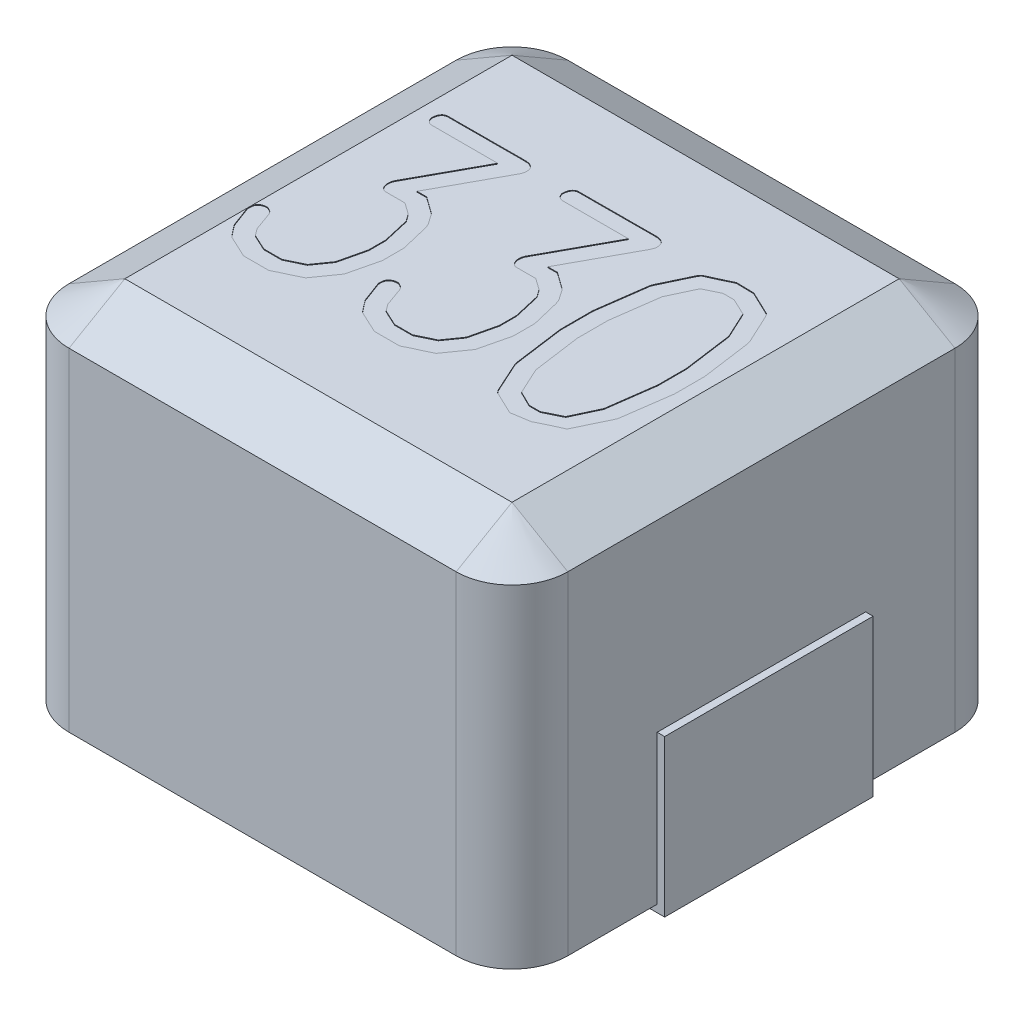
SolidWorks part; units mm, degrees
ref_plane "Front Plane" through (0, 0, 0) normal (0, 0, 1) x (1, 0, 0)
ref_plane "Top Plane" through (0, 0, 0) normal (0, 1, 0) x (1, 0, 0)
ref_plane "Right Plane" through (0, 0, 0) normal (1, 0, 0) x (0, 0, -1)
sketch "Sketch1" plane through (0, 0, 0) normal (0, 1, 0) x (1, 0, 0)
  line L0 (0, 6.4257) -> (0, -7.6623) construction
  line L1 (-1.025, 3.35) -> (1.025, 3.35) construction
  line L2 (-3.35, 1.525) -> (-3.35, -1.525) construction
  line L3 (-1.025, -3.35) -> (1.025, -3.35) construction
  line L4 (3.35, 1.525) -> (3.35, -1.525) construction
  line L5 (-1.675, 1.675) -> (1.675, -1.675) construction
  line L6 (-1.675, -1.675) -> (1.675, 1.675) construction
  line L7 (-1.175, 3.2) -> (-1.175, 1.825) construction
  line L8 (-1.325, 1.675) -> (-3.2, 1.675) construction
  line L9 (0, 0) -> (-4.3179, 0) construction
  line L10 (1.325, 1.675) -> (3.2, 1.675) construction
  line L11 (1.175, 3.2) -> (1.175, 1.825) construction
  line L12 (-1.325, -1.675) -> (-3.2, -1.675) construction
  line L13 (1.325, -1.675) -> (3.2, -1.675) construction
  line L14 (1.175, -3.2) -> (1.175, -1.825) construction
  line L15 (-1.175, -3.2) -> (-1.175, -1.825) construction
  line L16 (-3.35, 3.35) -> (-1.175, 3.35) construction
  line L17 (-3.35, 3.35) -> (-1.675, 1.675) construction
  line L18 (-3.35, 3.35) -> (-3.35, 1.675) construction
  line L19 (1.175, 3.35) -> (3.35, 3.35) construction
  line L20 (1.675, 1.675) -> (3.35, 3.35) construction
  line L21 (3.35, 3.35) -> (3.35, 1.675) construction
  line L22 (3.35, -1.675) -> (3.35, -3.35) construction
  line L23 (1.675, -1.675) -> (3.35, -3.35) construction
  line L24 (1.175, -3.35) -> (3.35, -3.35) construction
  line L25 (-3.35, -3.35) -> (-1.175, -3.35) construction
  line L26 (-3.35, -3.35) -> (-1.675, -1.675) construction
  line L27 (-3.35, -1.675) -> (-3.35, -3.35) construction
  line L29 (2.6, -3.35) -> (-2.6, -3.35)
  line L30 (3.35, -2.6) -> (3.35, 2.6)
  line L31 (2.6, 3.35) -> (-2.6, 3.35)
  line L32 (-3.35, -2.6) -> (-3.35, 2.6)
  line L33 (3.35, -3.35) -> (-3.35, 3.35) construction
  line L34 (3.35, 3.35) -> (-3.35, -3.35) construction
  arc A0 (3.35, -1.525) -> (3.2, -1.675) centre (3.2, -1.525) cw construction
  arc A1 (1.325, -1.675) -> (1.175, -1.825) centre (1.325, -1.825) ccw construction
  arc A2 (1.175, -3.2) -> (1.025, -3.35) centre (1.025, -3.2) cw construction
  arc A3 (-1.025, -3.35) -> (-1.175, -3.2) centre (-1.025, -3.2) cw construction
  arc A4 (-1.175, -1.825) -> (-1.325, -1.675) centre (-1.325, -1.825) ccw construction
  arc A5 (-3.2, -1.675) -> (-3.35, -1.525) centre (-3.2, -1.525) cw construction
  arc A6 (-3.35, 1.525) -> (-3.2, 1.675) centre (-3.2, 1.525) cw construction
  arc A7 (3.35, 1.525) -> (3.2, 1.675) centre (3.2, 1.525) ccw construction
  arc A8 (1.325, 1.675) -> (1.175, 1.825) centre (1.325, 1.825) cw construction
  arc A9 (1.175, 3.2) -> (1.025, 3.35) centre (1.025, 3.2) ccw construction
  arc A10 (-1.325, 1.675) -> (-1.175, 1.825) centre (-1.325, 1.825) ccw construction
  arc A11 (-1.175, 3.2) -> (-1.025, 3.35) centre (-1.025, 3.2) cw construction
  arc A12 (3.35, -2.6) -> (2.6, -3.35) centre (2.6, -2.6) cw
  arc A13 (-2.6, -3.35) -> (-3.35, -2.6) centre (-2.6, -2.6) cw
  arc A14 (3.35, 2.6) -> (2.6, 3.35) centre (2.6, 2.6) ccw
  arc A15 (-3.35, 2.6) -> (-2.6, 3.35) centre (-2.6, 2.6) cw
  point P0 (0, 0)
  point P38 (1.175, -1.675)
  point P47 (-1.175, -1.675)
  point P59 (1.175, 1.675)
  point P65 (-1.175, 1.675)
  dimension "D5" = 0.15
  dimension "D6" = 0.75
  dimension "D1" = 6.7
  dimension "D2" = 1.175
  dimension "D3" = 1.675
  dimension "D4" = 6.7
extrude "Boss-Extrude1" add sketch "Sketch1" along normal blind 4.9
sketch "Sketch4" plane through (0, 0, 0) normal (0, -1, 0) x (1, 0, 0)
  line L3 (0, 3.35) -> (0, -3.35) construction
  line L24 (-2.6, 3.35) -> (2.6, 3.35) construction
  line L25 (2.6, -3.35) -> (-2.6, -3.35) construction
  line L26 (-3.45, 1.4) -> (-2, 1.4)
  line L28 (-2, 1.4) -> (-2, -1.4)
  line L29 (-2, -1.4) -> (-3.45, -1.4)
  line L30 (-3.45, -1.4) -> (-3.45, 1.4)
  line L31 (0, 0) -> (-5.1227, 0) construction
  line L32 (2, -1.4) -> (3.45, -1.4)
  line L33 (2, 1.4) -> (2, -1.4)
  line L34 (3.45, 1.4) -> (2, 1.4)
  line L35 (3.45, -1.4) -> (3.45, 1.4)
  line L36 (-3.35, -2.6) -> (-3.35, 2.6) construction
  dimension "D1" = 2.8
  dimension "D2" = 4
  dimension "D3" = 0.1
extrude "Boss-Extrude3" add sketch "Sketch4" against normal blind 2 and the other way blind 0.1
chamfer "Chamfer1" distance 0.75 angle 30 8 edges at (0, 4.9, -3.35) (-3.1303, 4.9, -3.1303) (3.1303, 4.9, -3.1303) (-3.35, 4.9, 0) (3.35, 4.9, 0) (-3.1303, 4.9, 3.1303) (3.1303, 4.9, 3.1303) (0, 4.9, 3.35) first distance on face at (0, 4.9, 0)
sketch "Sketch5" plane through (0, 4.9, 0) normal (0, 1, 0) x (1, 0, 0)
  line L0 (-2.6, -1.5) -> (2.6, -1.5) construction
  line L1 (0, 3.35) -> (0, -3.35) construction
  line L2 (-2.6, 3.35) -> (2.6, 3.35) construction
  line L3 (2.6, -3.35) -> (-2.6, -3.35) construction
  line L4 (-2.6, 2.6) -> (-2.6, -2.6) construction
  text T0 "330\r\n" font "SWSimp" height 3
  dimension "D1" = 1.5
extrude "Cut-Extrude1" cut sketch "Sketch5" against normal blind 0.01
